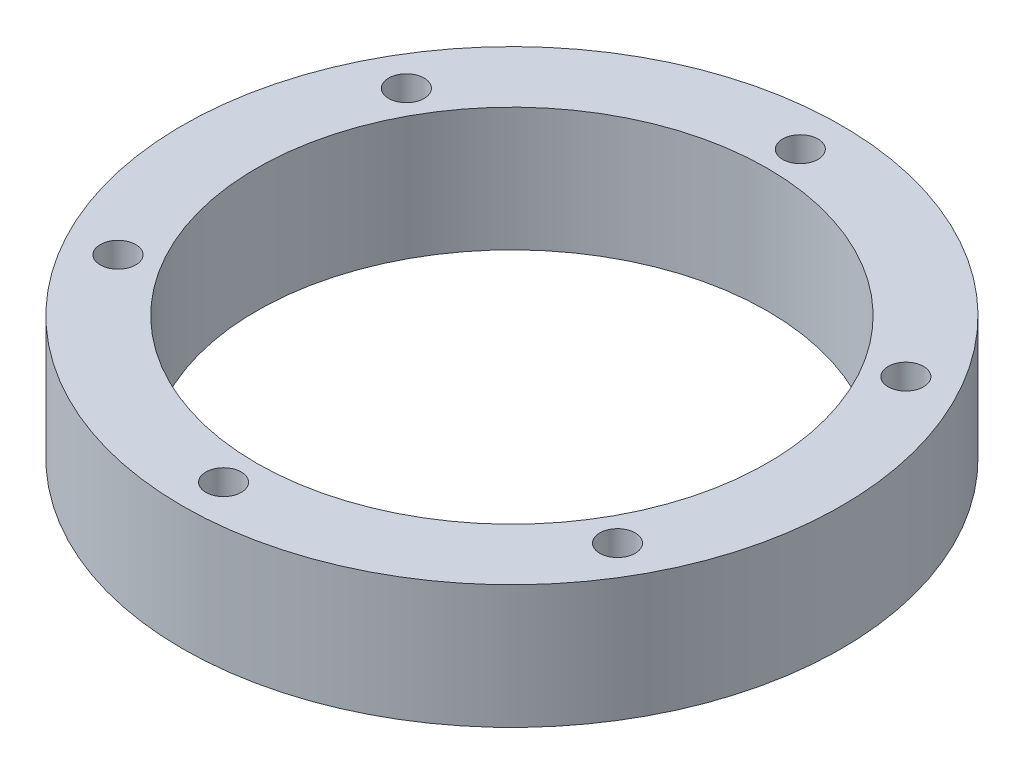
SolidWorks part; units mm, degrees
ref_plane "前视基准面" through (0, 0, 0) normal (0, 0, 1) x (1, 0, 0)
ref_plane "上视基准面" through (0, 0, 0) normal (0, 1, 0) x (1, 0, 0)
ref_plane "右视基准面" through (0, 0, 0) normal (1, 0, 0) x (0, 0, -1)
other "Configuration Table"
sketch "草图1" plane through (0, 0, 0) normal (0, 1, 0) x (1, 0, 0)
  circle A0 centre (0, 0) radius 31
  circle A1 centre (0, 0) radius 35
  circle A2 centre (0, 0) radius 40
  circle A3 centre (0, 35) radius 2.15
  circle A4 centre (30.3109, 17.5) radius 2.15
  circle A5 centre (30.3109, -17.5) radius 2.15
  circle A6 centre (0, -35) radius 2.15
  circle A7 centre (-30.3109, -17.5) radius 2.15
  circle A8 centre (-30.3109, 17.5) radius 2.15
  point P20 (0, 0)
  dimension "D1" = 62
  dimension "D2" = 70
  dimension "D3" = 80
  dimension "D4" = 4.3
  dimension "D5" = 6
extrude "凸台-拉伸3" add sketch "草图1" along normal blind 15 contours A8 A1 A7 A6 A5 A4 A3 A0 | A2 A8 A1 A3 A4 A5 A6 A7 region at (33.107, 0, 7.7895) region at (-38.8686, 0, 0)
